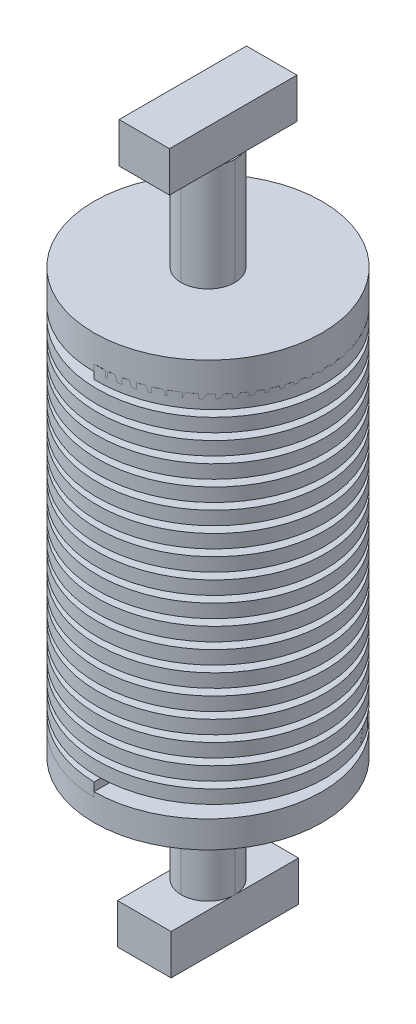
SolidWorks part; units mm, degrees
ref_plane "Front Plane" through (0, 0, 0) normal (0, 0, 1) x (1, 0, 0)
ref_plane "Top Plane" through (0, 0, 0) normal (0, 1, 0) x (1, 0, 0)
ref_plane "Right Plane" through (0, 0, 0) normal (1, 0, 0) x (0, 0, -1)
sketch "Sketch1" plane through (0, 0, 0) normal (0, 1, 0) x (1, 0, 0)
  circle A0 centre (0, 0) radius 7.5
curve "Helix/Spiral1" pitch 1.5 height 27 radius 7.5 left hand yes centre (0, 0, 0) axis (0, 1, 0) start towards (0, 0, 1)
sketch "Sketch4" plane through (0, 0, 0) normal (0, 0, 1) x (1, 0, 0)
  line L1 (-8.5, 1) -> (-4.5, 1)
  line L2 (-8.5, 1) -> (-8.5, 0)
  line L3 (-8.5, 0) -> (-4.5, 0)
  line L4 (-4.5, 1) -> (-4.5, 0)
  line L5 (-8.5, 1) -> (-4.5, 0) construction
  line L6 (-8.5, 0) -> (-4.5, 1) construction
  point P0 (-5.6693, 0.2923)
  dimension "D1" = 1
  dimension "D2" = 4
sweep "Sweep1" add profiles "Sketch4" path "Helix/Spiral1"
sketch "Sketch5" plane through (0, 0, 0) normal (0, 1, 0) x (1, 0, 0)
  circle A0 centre (0, 0) radius 8.5
extrude "Boss-Extrude1" add sketch "Sketch5" against normal blind 2
sketch "Sketch15" plane through (0, -2, 0) normal (0, -1, 0) x (1, 0, 0)
  line L1 (-2, -2) -> (2, -2)
  line L2 (-2, -2) -> (-2, 2)
  line L3 (-2, 2) -> (2, 2)
  line L4 (2, -2) -> (2, 2)
  line L5 (-2, -2) -> (2, 2) construction
  line L6 (-2, 2) -> (2, -2) construction
  point P0 (0, 0)
  dimension "D1" = 4
  dimension "D2" = 4
extrude "Boss-Extrude16" add sketch "Sketch15" along normal blind 8
sketch "Sketch19" plane through (-2, 0, 0) normal (-1, 0, 0) x (0, 0, 1)
  line L0 (-2, -10) -> (-2, -2) construction
  line L1 (-4.75, -9.9055) -> (4.75, -9.9055)
  line L2 (-4.75, -9.9055) -> (-4.75, -12.9055)
  line L3 (-4.75, -12.9055) -> (4.75, -12.9055)
  line L4 (4.75, -9.9055) -> (4.75, -12.9055)
  dimension "D1" = 2.75
  dimension "D2" = 9.5
  dimension "D3" = 3
extrude "Boss-Extrude17" add sketch "Sketch19" against normal blind 4
fillet "Fillet1" radius 2 4 edges at (2, -5.9528, -2) (2, -5.9528, 2) (-2, -5.9528, 2) (-2, -5.9528, -2)
sketch3d "3DSketch1" plane through (0, 0, 0) normal (0, 0, 1) x (1, 0, 0)
  dimension "D1" = 90
sketch "Sketch20" plane through (0, 27.625, 0) normal (0, 1, 0) x (1, 0, 0)
  circle A0 centre (0, 0) radius 8.5
extrude "Boss-Extrude19" add sketch "Sketch20" along normal blind 2 and the other way blind 0.5 separate body
sketch "Sketch21" plane through (0, 29.625, 0) normal (0, 1, 0) x (1, 0, 0)
  line L1 (-2, -2) -> (2, -2)
  line L2 (-2, -2) -> (-2, 2)
  line L3 (-2, 2) -> (2, 2)
  line L4 (2, -2) -> (2, 2)
  line L5 (-2, -2) -> (2, 2) construction
  line L6 (-2, 2) -> (2, -2) construction
  point P0 (0, 0)
  dimension "D1" = 4
  dimension "D2" = 4
extrude "Boss-Extrude20" add sketch "Sketch21" along normal blind 8
sketch "Sketch22" plane through (2, 0, 0) normal (1, 0, 0) x (0, 0, -1)
  line L0 (2, 37.625) -> (2, 29.625) construction
  line L1 (4.75, 37.5893) -> (-4.75, 37.5893)
  line L2 (4.75, 37.5893) -> (4.75, 40.5893)
  line L3 (4.75, 40.5893) -> (-4.75, 40.5893)
  line L4 (-4.75, 37.5893) -> (-4.75, 40.5893)
  dimension "D1" = 9.5
  dimension "D2" = 3
  dimension "D3" = 2.75
extrude "Boss-Extrude21" add sketch "Sketch22" against normal blind 4
fillet "Fillet2" radius 2 4 edges at (-2, 33.6072, 2) (2, 33.6072, 2) (2, 33.6072, -2) (-2, 33.6072, -2)
sketch "Sketch24" plane through (0, 40.5893, 0) normal (0, 1, 0) x (1, 0, 0)
  line L0 (-2, -4.75) -> (2, -4.75) construction
  line L1 (-2, 4.75) -> (-1.88, 4.75)
  line L2 (-2, 4.75) -> (-2, -4.75)
  line L3 (-2, -4.75) -> (-1.88, -4.75)
  line L4 (-1.88, 4.75) -> (-1.88, -4.75)
  line L6 (2, 4.75) -> (1.88, 4.75)
  line L7 (2, 4.75) -> (2, -4.75)
  line L8 (2, -4.75) -> (1.88, -4.75)
  line L9 (1.88, 4.75) -> (1.88, -4.75)
  dimension "D1" = 0.12
  dimension "D2" = 0.12
extrude "Cut-Extrude3" cut sketch "Sketch24" against normal blind 3
